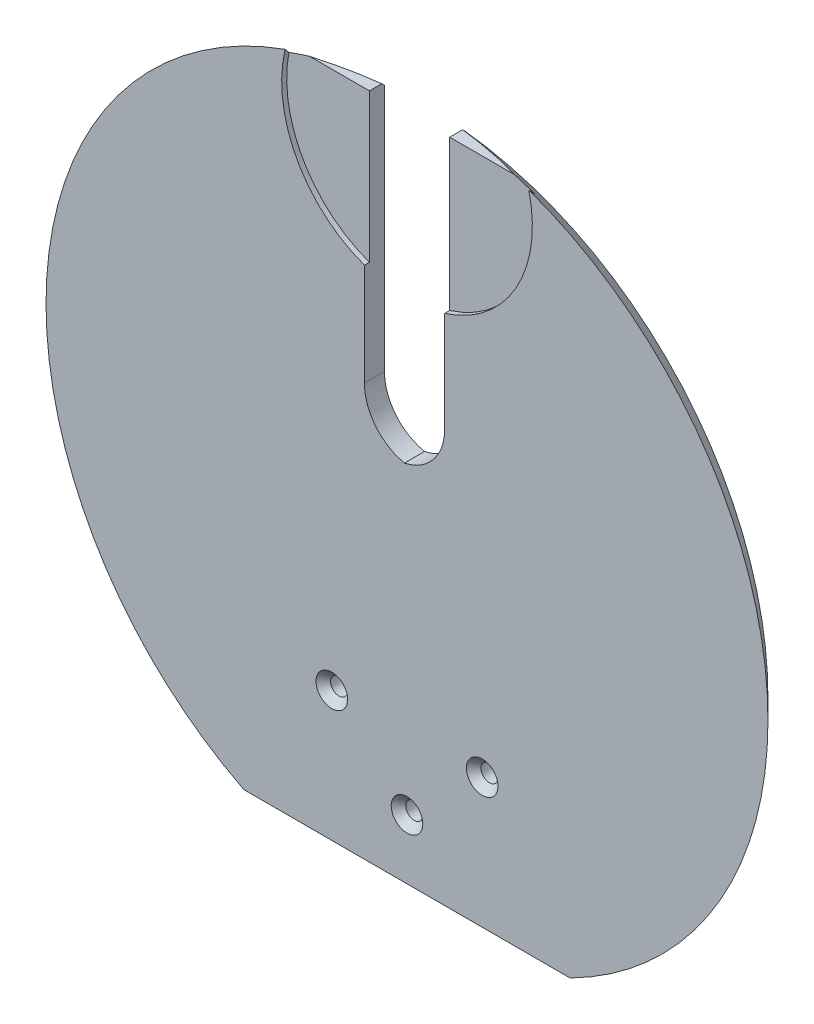
SolidWorks part; units mm, degrees
material "PET"
ref_plane "Front Plane" through (0, 0, 0) normal (0, 0, 1) x (1, 0, 0)
ref_plane "Top Plane" through (0, 0, 0) normal (0, 1, 0) x (1, 0, 0)
ref_plane "Right Plane" through (0, 0, 0) normal (1, 0, 0) x (0, 0, -1)
sketch "Sketch1" plane through (0, 0, 0) normal (0, 0, 1) x (1, 0, 0)
  line L0 (-9.944, -71.31) -> (9.944, -71.31) construction
  line L1 (-66.4124, -27.81) -> (66.4124, -27.81) construction
  line L2 (-35.1981, -62.81) -> (35.1981, -62.81) construction
  line L3 (0, -27.81) -> (0, -62.81) construction
  line L4 (-23.6643, 68) -> (23.6643, 68)
  line L5 (-31.3634, -64.81) -> (31.3634, -64.81)
  arc A0 (-23.6643, 68) -> (23.6643, 68) centre (0, 0) ccw
  circle A1 centre (0, -52.31) radius 2.397 construction
  circle A2 centre (-15, -38.31) radius 2.5305 construction
  circle A3 centre (15, -38.31) radius 2.5603 construction
  arc A4 (23.6643, 68) -> (-23.6643, 68) centre (0, 0) ccw construction
  point P13 (0, -45.31)
  dimension "D1" = 144
  dimension "D2" = 71.31
  dimension "D3" = 43.5
  dimension "D4" = 35
  dimension "D5" = 7
  dimension "D6" = 15
  dimension "D7" = 15
  dimension "D8" = 7
  dimension "D9" = 68
  dimension "D10" = 2
extrude "Boss-Extrude2" add sketch "Sketch1" along normal blind 4 contours A0 L4
sketch "Sketch2" plane through (0, 0, 4) normal (0, 0, 1) x (1, 0, 0)
  point P0 (15, -38.31)
  point P3 (-15, -38.31)
  point P6 (0, -52.31)
hole_wizard "CSK for M3 Countersunk Flat Head Screw1" positions "Sketch2" profile "Sketch3" countersink size "M3" standard "ISO"
sketch "Sketch3" plane through (15, -38.31, 4) normal (1, 0, 0) x (0, -1, 0)
  line L0 (0, 0) -> (0, 5.0215)
  line L1 (0, 5.0215) -> (1.7, 4)
  line L2 (1.7, 4) -> (1.7, 1.45)
  line L3 (1.7, 1.45) -> (3.15, 0)
  line L5 (3.15, 0) -> (0, 0)
  line L6 (-1.7, 1.45) -> (-3.15, 0) construction
  line L10 (0, 5.0215) -> (-1.7, 4) construction
  line L11 (0, -6.35) -> (0, 107.95) construction
  dimension "Hole Dia." = 3.4
  dimension "Hole Depth" = 4
  dimension "Near C'Sink Dia." = 6.3
  dimension "Near C'Sink Angle" = 90
  dimension "Drill Angle" = 118
sketch "Sketch4" plane through (0, 0, 4) normal (0, 0, 1) x (1, 0, 0)
  line L5 (23.6643, 68) -> (-23.6643, 68)
  line L6 (23.6643, 68) -> (-23.6643, 68)
  line L7 (-8.5, 8) -> (7.5, 8)
  line L8 (-8.5, 8) -> (-8.5, 68)
  line L9 (-8.5, 68) -> (7.5, 68)
  line L10 (7.5, 8) -> (7.5, 68)
  arc A1 (-23.6643, 68) -> (23.6643, 68) centre (0, 0) ccw
  arc A2 (-23.6643, 68) -> (23.6643, 68) centre (0, 0) ccw
  dimension "D1" = 60
  dimension "D3" = 16
  dimension "D4" = 0
extrude "Cut-Extrude1" cut sketch "Sketch4" against normal up to surface (4 mm away) contours L7 L10 L6 L8 region at (-0.5, 38, 4) up to face at (0, -2, 0)
sketch "Sketch5" plane through (0, 0, 4) normal (0, 0, 1) x (1, 0, 0)
  circle A0 centre (0, 61.9) radius 25
  dimension "D1" = 50
  dimension "D2" = 61.9
extrude "Cut-Extrude2" cut sketch "Sketch5" against normal blind 1
fillet "Fillet1" radius 10 2 edges at (-8.5, 8, 2) (7.5, 8, 2)
extrude "Cut-Extrude3" cut sketch "Sketch1<3>" along normal blind 21 contours L5 A0 region at (0, -67.6987, 0)
sketch "Sketch1<3>" plane through (0, 0, 0) normal (0, 0, 1) x (1, 0, 0) same geometry as "Sketch1"
chamfer "Chamfer2" distance 5 angle 30 1 edges at (0, -64.81, 0) first distance on face at (0, -64.81, 2)
chamfer "Chamfer3" distance 4 angle 45 2 edges at (-71.6383, 7.2074, 0) (71.6383, 7.2074, 0)
